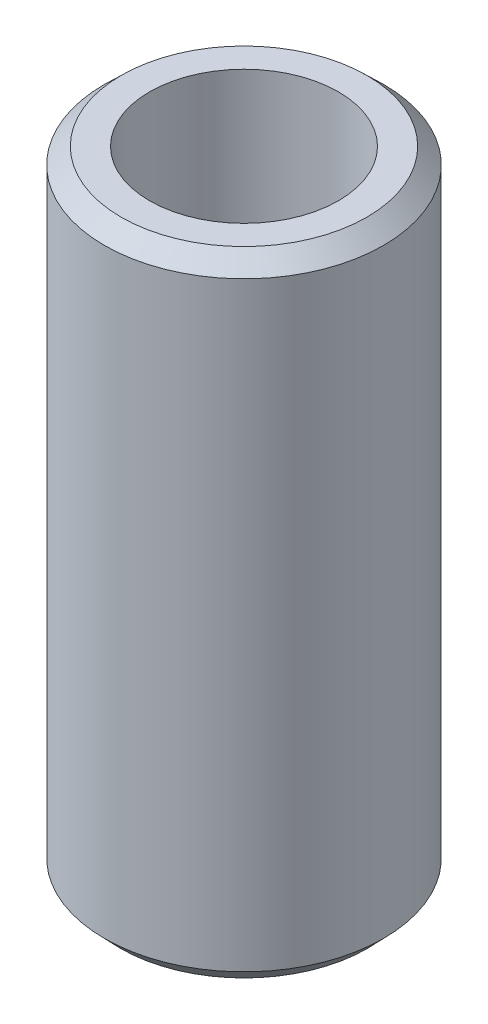
SolidWorks part; units mm, degrees
ref_plane "Front Plane" through (0, 0, 0) normal (0, 0, 1) x (1, 0, 0)
ref_plane "Top Plane" through (0, 0, 0) normal (0, 1, 0) x (1, 0, 0)
ref_plane "Right Plane" through (0, 0, 0) normal (1, 0, 0) x (0, 0, -1)
sketch "Sketch1" plane through (0, 0, 0) normal (0, 1, 0) x (1, 0, 0)
  circle A0 centre (0, 0) radius 22.5
  dimension "SHAFT_OD" = 45
extrude "Boss-Extrude1" add sketch "Sketch1" along normal blind 102.0637
sketch "Sketch2" plane through (0, 0, 0) normal (0, 1, 0) x (1, 0, 0)
  circle A0 centre (0, 0) radius 15.2227
  dimension "BORE_D" = 30.4454
extrude "Cut-Extrude1" cut sketch "Sketch2" along normal through all
chamfer "Chamfer1" distance 2.5963 angle 46.057 2 edges at (0, 102.0637, 22.5) (0, 0, 22.5) first distance on face at (0, 102.0637, 22.5) first distance on face at (0, 0, 15.2227)
